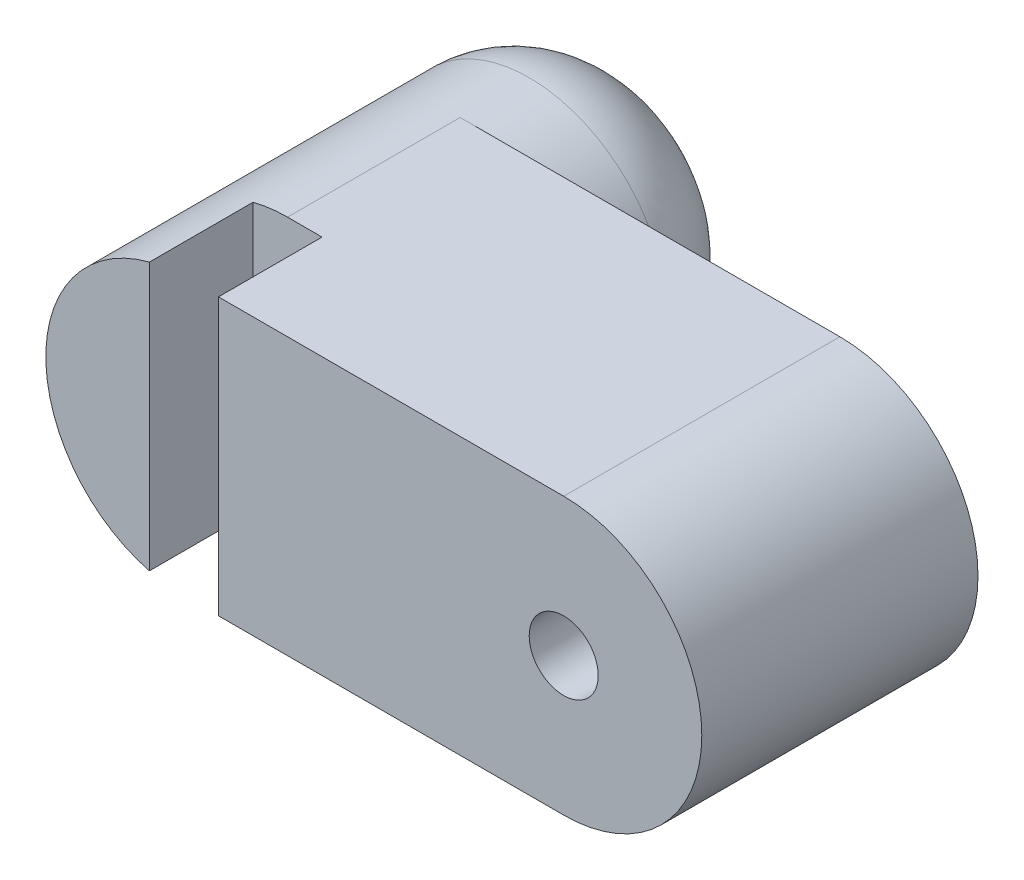
SolidWorks part; units mm, degrees
ref_plane "前视基准面" through (0, 0, 0) normal (0, 0, 1) x (1, 0, 0)
ref_plane "上视基准面" through (0, 0, 0) normal (0, 1, 0) x (1, 0, 0)
ref_plane "右视基准面" through (0, 0, 0) normal (1, 0, 0) x (0, 0, -1)
other "Configuration Table"
sketch "草图1" plane through (0, 0, 0) normal (0, 0, 1) x (1, 0, 0)
  circle A0 centre (0, 0) radius 2
  circle A1 centre (0, 0) radius 0.5
  dimension "D1" = 4
  dimension "D2" = 1
extrude "凸台-拉伸1" add sketch "草图1" along normal blind 6.5
fillet "圆角2" radius 1.5 1 edges at (2, 0, 0)
sketch "草图3" plane through (0, 0, 0) normal (0, 1, 0) x (1, 0, 0)
  line L0 (0, 0) -> (0, -2.5) construction
  line L1 (0, -2.5) -> (0, -6.5)
  line L2 (0, -2.5) -> (5.5, -2.5)
  line L3 (5.5, -2.5) -> (5.5, -6.5)
  line L4 (0, -6.5) -> (5.5, -6.5)
  dimension "D1" = 2.5
  dimension "D2" = 4
  dimension "D3" = 5.5
  dimension "D4" = 4
extrude "凸台-拉伸2" add sketch "草图3" along normal mid plane 4
sketch "草图4" plane through (0, 0, 2.5) normal (0, 0, -1) x (-1, 0, 0)
  line L0 (-5.5, 2) -> (-5.5, -2) construction
  circle A0 centre (-5.5, 0) radius 2
  circle A1 centre (-5.5, 0) radius 0.5
  dimension "D1" = 1
extrude "凸台-拉伸3" add sketch "草图4" against normal blind 4
sketch "草图5" plane through (0, 0, 2.5) normal (0, 0, -1) x (-1, 0, 0)
  line L0 (-5.5, 0.5) -> (-5.5, -0.5) construction
  circle A0 centre (-5.5, 0) radius 0.5
  dimension "D1" = 1
extrude "切除-拉伸2" cut sketch "草图5" against normal blind 4
sketch "草图6" plane through (0, 0, 6.5) normal (0, 0, 1) x (1, 0, 0)
  circle A0 centre (0, 0) radius 0.5
  dimension "D1" = 1
extrude "切除-拉伸3" cut sketch "草图6" against normal through all
sketch "草图2" plane through (0, 0, 6.5) normal (0, 0, 1) x (1, 0, 0)
  line L1 (-0.5, -2.0824) -> (0.5, -2.0824)
  line L2 (-0.5, -2.0824) -> (-0.5, 2.0824)
  line L3 (-0.5, 2.0824) -> (0.5, 2.0824)
  line L4 (0.5, -2.0824) -> (0.5, 2.0824)
  line L5 (-0.5, -2.0824) -> (0.5, 2.0824) construction
  line L6 (-0.5, 2.0824) -> (0.5, -2.0824) construction
  point P0 (0, 0)
  dimension "D1" = 1
extrude "切除-拉伸1" cut sketch "草图2" against normal blind 1.5
